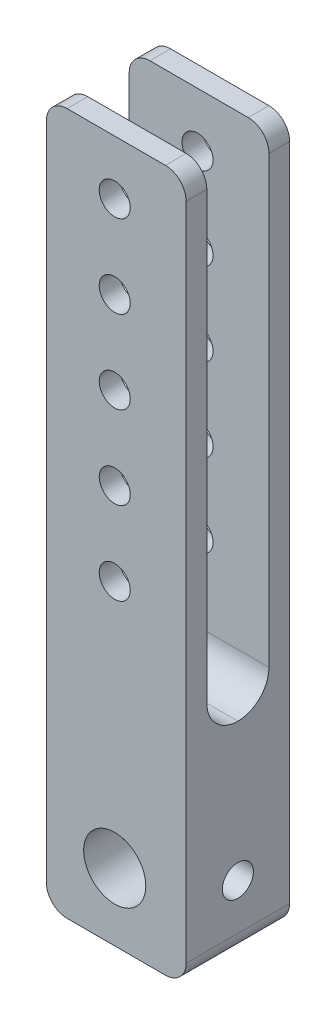
SolidWorks part; units mm, degrees
ref_plane "Front Plane" through (0, 0, 0) normal (0, 0, 1) x (1, 0, 0)
ref_plane "Top Plane" through (0, 0, 0) normal (0, 1, 0) x (1, 0, 0)
ref_plane "Right Plane" through (0, 0, 0) normal (1, 0, 0) x (0, 0, -1)
sketch "Sketch1" plane through (0, 0, 0) normal (0, 0, 1) x (1, 0, 0)
  line L1 (0, 0) -> (21.4312, 0)
  line L2 (0, 0) -> (0, 107.5531)
  line L3 (0, 107.5531) -> (21.4312, 107.5531)
  line L4 (21.4312, 0) -> (21.4312, 107.5531)
  circle A0 centre (10.4846, 10.3187) radius 4.7625
  circle A1 centre (10.4846, 99.2188) radius 2.3812
  circle A2 centre (10.4846, 86.5187) radius 2.3812
  circle A3 centre (10.4846, 73.8188) radius 2.3812
  circle A4 centre (10.4846, 61.1188) radius 2.3812
  circle A5 centre (10.4846, 48.4188) radius 2.3812
  dimension "D3" = 9.525
  dimension "D5" = 4.7625
  dimension "D6" = 8.3344
  dimension "D7" = 4.7625
  dimension "D8" = 12.7
  dimension "D9" = 4.7625
  dimension "D10" = 4.7625
  dimension "D11" = 4.7625
  dimension "D12" = 12.7
  dimension "D13" = 12.7
  dimension "D14" = 12.7
  dimension "D1" = 107.5531
  dimension "D2" = 21.4312
  dimension "D4" = 10.3187
extrude "Boss-Extrude3" add sketch "Sketch1" along normal blind 15.875
fillet "Fillet1" radius 3.175 1 edges at (21.4312, 0, 7.9375)
fillet "Fillet2" radius 3.175 1 edges at (0, 0, 7.9375)
fillet "Fillet3" radius 3.175 1 edges at (21.4312, 107.5531, 7.9375)
fillet "Fillet4" radius 3.175 1 edges at (0, 107.5531, 7.9375)
sketch "Sketch3" plane through (0, 0, 0) normal (1, 0, 0) x (0, 0, -1)
  line L0 (-15.875, 107.5531) -> (0, 107.5531) construction
  line L1 (-12.7, 107.5531) -> (-3.175, 107.5531)
  line L2 (-12.7, 107.5531) -> (-12.7, 31.3531)
  line L3 (-12.7, 31.3531) -> (-3.175, 31.3531)
  line L4 (-3.175, 107.5531) -> (-3.175, 31.3531)
  line L5 (-15.875, 3.175) -> (-15.875, 104.3781) construction
  line L6 (0, 3.175) -> (0, 104.3781) construction
  dimension "D1" = 9.525
  dimension "D2" = 3.175
  dimension "D3" = 76.2
  dimension "D4" = 3.175
extrude "Cut-Extrude2" cut sketch "Sketch3" along normal through all contours L2 L1 L4 L3
fillet "Fillet5" radius 4.7625 1 edges at (10.7156, 31.3531, 3.175)
fillet "Fillet6" radius 4.7625 1 edges at (10.7156, 31.3531, 12.7)
sketch "Sketch5" plane through (0, 0, 0) normal (1, 0, 0) x (0, 0, -1)
  line L0 (0, 3.175) -> (0, 104.3781) construction
  line L2 (0, 0) -> (-15.875, 0) construction
  circle A1 centre (-7.9375, 10.2044) radius 2.3813
  point P4 (-7.9375, 10.2044)
  dimension "D1" = 4.7625
  dimension "D3" = 7.9375
  dimension "D2" = 10.2044
extrude "Cut-Extrude3" cut sketch "Sketch5" along normal blind 21.4312
